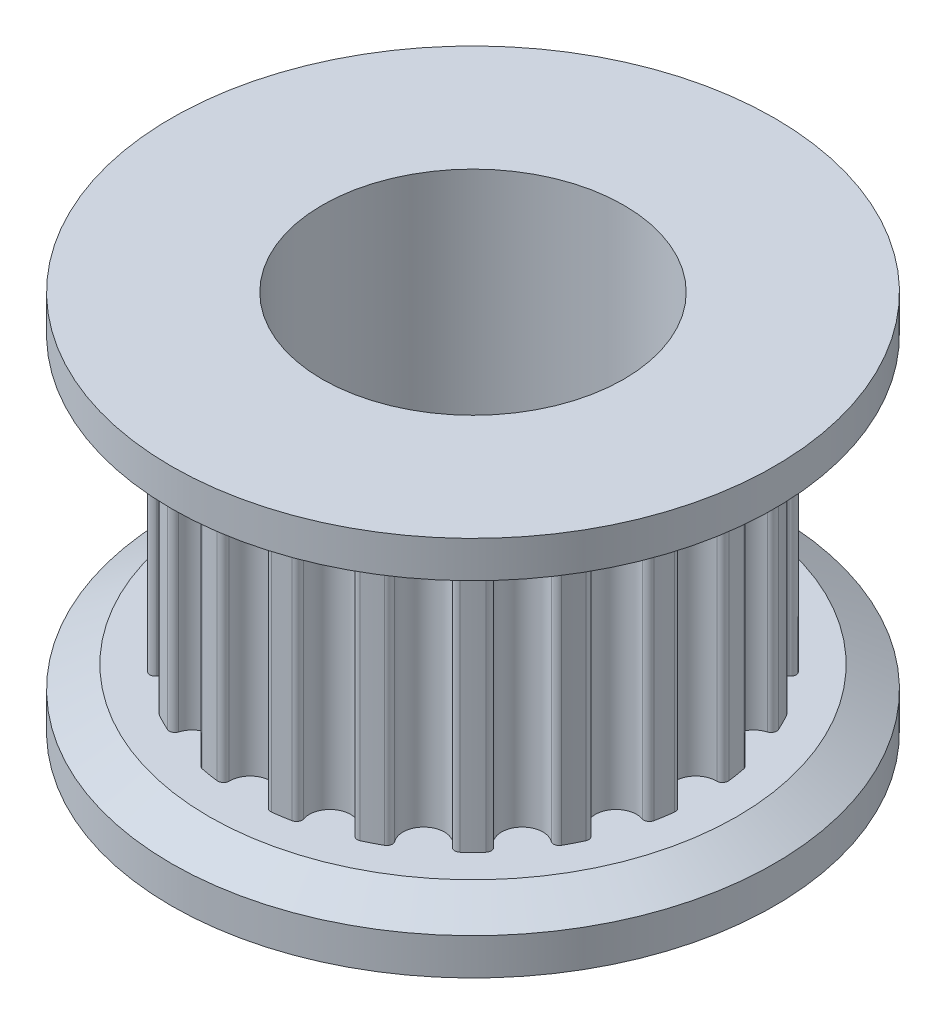
SolidWorks part; units mm, degrees
note: '?' marks a value the reader was unsure of.
material "1060 Сплав"
ref_plane "Спереди" through (0, 0, 0) normal (0, 0, 1) x (1, 0, 0)
ref_plane "Сверху" through (0, 0, 0) normal (0, 1, 0) x (1, 0, 0)
ref_plane "Справа" through (0, 0, 0) normal (1, 0, 0) x (0, 0, -1)
other "Configuration Table"
sketch "Эскиз1" plane through (0, 0, 0) normal (0, 1, 0) x (1, 0, 0)
  circle A0 centre (0, 0) radius 8
  circle A1 centre (0, 0) radius 2.5
  dimension "D1" = 16
  dimension "D2" = 5
extrude "Бобышка-Вытянуть1" add sketch "Эскиз1" along normal blind 7.45
sketch "Эскиз2" plane through (0, 7.45, 0) normal (0, 1, 0) x (1, 0, 0)
  arc A0 (-2.5575, 5.549) -> (-2.986, 5.3307) centre (0, 0) ccw
  circle A1 centre (0, 0) radius 2.5 construction
  circle A2 centre (0, 0) radius 2.5
  arc A3 (-0.55, 5.9169) -> (0.55, 5.9169) centre (0, 5.91) ccw
  arc A4 (1.3054, 5.7972) -> (2.3515, 5.4573) centre (1.8263, 5.6207) ccw
  arc A5 (3.0329, 5.1101) -> (3.9228, 4.4636) centre (3.4738, 4.7813) ccw
  arc A6 (4.4636, 3.9228) -> (5.1101, 3.0329) centre (4.7813, 3.4738) ccw
  arc A7 (5.4573, 2.3515) -> (5.7972, 1.3054) centre (5.6207, 1.8263) ccw
  arc A8 (5.9169, 0.55) -> (5.9169, -0.55) centre (5.91, 0) ccw
  arc A9 (5.7972, -1.3054) -> (5.4573, -2.3515) centre (5.6207, -1.8263) ccw
  arc A10 (5.1101, -3.0329) -> (4.4636, -3.9228) centre (4.7813, -3.4738) ccw
  arc A11 (3.9228, -4.4636) -> (3.0329, -5.1101) centre (3.4738, -4.7813) ccw
  arc A12 (2.3515, -5.4573) -> (1.3054, -5.7972) centre (1.8263, -5.6207) ccw
  arc A13 (0.55, -5.9169) -> (-0.55, -5.9169) centre (0, -5.91) ccw
  arc A14 (-1.3054, -5.7972) -> (-2.3515, -5.4573) centre (-1.8263, -5.6207) ccw
  arc A15 (-3.0329, -5.1101) -> (-3.9228, -4.4636) centre (-3.4738, -4.7813) ccw
  arc A16 (-4.4636, -3.9228) -> (-5.1101, -3.0329) centre (-4.7813, -3.4738) ccw
  arc A17 (-5.4573, -2.3515) -> (-5.7972, -1.3054) centre (-5.6207, -1.8263) ccw
  arc A18 (-5.9169, -0.55) -> (-5.9169, 0.55) centre (-5.91, 0) ccw
  arc A19 (-5.7972, 1.3054) -> (-5.4573, 2.3515) centre (-5.6207, 1.8263) ccw
  arc A20 (-5.1101, 3.0329) -> (-4.4636, 3.9228) centre (-4.7813, 3.4738) ccw
  arc A21 (-3.9228, 4.4636) -> (-3.0329, 5.1101) centre (-3.4738, 4.7813) ccw
  arc A22 (-2.3515, 5.4573) -> (-1.3054, 5.7972) centre (-1.8263, 5.6207) ccw
  arc A23 (-4.147, 4.4871) -> (-4.4871, 4.147) centre (0, 0) ccw
  arc A24 (-0.7176, 6.0677) -> (-1.1926, 5.9925) centre (0, 0) ccw
  arc A25 (1.1926, 5.9925) -> (0.7176, 6.0677) centre (0, 0) ccw
  arc A26 (2.986, 5.3307) -> (2.5575, 5.549) centre (0, 0) ccw
  arc A27 (4.4871, 4.147) -> (4.147, 4.4871) centre (0, 0) ccw
  arc A28 (5.549, 2.5575) -> (5.3307, 2.986) centre (0, 0) ccw
  arc A29 (6.0677, 0.7176) -> (5.9925, 1.1926) centre (0, 0) ccw
  arc A30 (-5.3307, 2.986) -> (-5.549, 2.5575) centre (0, 0) ccw
  arc A31 (-5.9925, 1.1926) -> (-6.0677, 0.7176) centre (0, 0) ccw
  arc A32 (-6.0677, -0.7176) -> (-5.9925, -1.1926) centre (0, 0) ccw
  arc A33 (-5.549, -2.5575) -> (-5.3307, -2.986) centre (0, 0) ccw
  arc A34 (-4.4871, -4.147) -> (-4.147, -4.4871) centre (0, 0) ccw
  arc A35 (-2.986, -5.3307) -> (-2.5575, -5.549) centre (0, 0) ccw
  arc A36 (5.9925, -1.1926) -> (6.0677, -0.7176) centre (0, 0) ccw
  arc A37 (5.3307, -2.986) -> (5.549, -2.5575) centre (0, 0) ccw
  arc A38 (4.147, -4.4871) -> (4.4871, -4.147) centre (0, 0) ccw
  arc A39 (2.5575, -5.549) -> (2.986, -5.3307) centre (0, 0) ccw
  arc A40 (0.7176, -6.0677) -> (1.1926, -5.9925) centre (0, 0) ccw
  arc A41 (-1.1926, -5.9925) -> (-0.7176, -6.0677) centre (0, 0) ccw
  arc A42 (5.9169, 0.55) -> (6.0677, 0.7176) centre (5.9188, 0.6999) ccw
  arc A43 (5.7972, 1.3054) -> (5.9925, 1.1926) centre (5.8454, 1.1633) cw
  arc A44 (5.4573, 2.3515) -> (5.549, 2.5575) centre (5.4128, 2.4947) ccw
  arc A45 (5.1101, 3.0329) -> (5.3307, 2.986) centre (5.1998, 2.9127) cw
  arc A46 (5.1101, -3.0329) -> (5.3307, -2.986) centre (5.1998, -2.9127) ccw
  arc A47 (5.4573, -2.3515) -> (5.549, -2.5575) centre (5.4128, -2.4947) cw
  arc A48 (5.7972, -1.3054) -> (5.9925, -1.1926) centre (5.8454, -1.1633) ccw
  arc A49 (5.9169, -0.55) -> (6.0677, -0.7176) centre (5.9188, -0.6999) cw
  arc A50 (3.9228, -4.4636) -> (4.147, -4.4871) centre (4.0452, -4.377) ccw
  arc A51 (4.4636, -3.9228) -> (4.4871, -4.147) centre (4.377, -4.0452) cw
  arc A52 (3.0329, -5.1101) -> (2.986, -5.3307) centre (2.9127, -5.1998) cw
  arc A53 (1.3054, -5.7972) -> (1.1926, -5.9925) centre (1.1633, -5.8454) cw
  arc A54 (0.55, -5.9169) -> (0.7176, -6.0677) centre (0.6999, -5.9188) ccw
  arc A55 (-0.55, -5.9169) -> (-0.7176, -6.0677) centre (-0.6999, -5.9188) cw
  arc A56 (-1.3054, -5.7972) -> (-1.1926, -5.9925) centre (-1.1633, -5.8454) ccw
  arc A57 (-2.3515, -5.4573) -> (-2.5575, -5.549) centre (-2.4947, -5.4128) cw
  arc A58 (-3.0329, -5.1101) -> (-2.986, -5.3307) centre (-2.9127, -5.1998) ccw
  arc A59 (-3.9228, -4.4636) -> (-4.147, -4.4871) centre (-4.0452, -4.377) cw
  arc A60 (-4.4636, -3.9228) -> (-4.4871, -4.147) centre (-4.377, -4.0452) ccw
  arc A61 (-5.9169, -0.55) -> (-6.0677, -0.7176) centre (-5.9188, -0.6999) ccw
  arc A62 (-5.7972, -1.3054) -> (-5.9925, -1.1926) centre (-5.8454, -1.1633) cw
  arc A63 (-5.4573, -2.3515) -> (-5.549, -2.5575) centre (-5.4128, -2.4947) ccw
  arc A64 (-5.1101, -3.0329) -> (-5.3307, -2.986) centre (-5.1998, -2.9127) cw
  arc A65 (-5.1101, 3.0329) -> (-5.3307, 2.986) centre (-5.1998, 2.9127) ccw
  arc A66 (-5.4573, 2.3515) -> (-5.549, 2.5575) centre (-5.4128, 2.4947) cw
  arc A67 (-5.7972, 1.3054) -> (-5.9925, 1.1926) centre (-5.8454, 1.1633) ccw
  arc A68 (-5.9169, 0.55) -> (-6.0677, 0.7176) centre (-5.9188, 0.6999) cw
  arc A69 (-4.4636, 3.9228) -> (-4.4871, 4.147) centre (-4.377, 4.0452) cw
  arc A70 (-3.9228, 4.4636) -> (-4.147, 4.4871) centre (-4.0452, 4.377) ccw
  arc A71 (-3.0329, 5.1101) -> (-2.986, 5.3307) centre (-2.9127, 5.1998) cw
  arc A72 (-2.3515, 5.4573) -> (-2.5575, 5.549) centre (-2.4947, 5.4128) ccw
  arc A73 (-1.3054, 5.7972) -> (-1.1926, 5.9925) centre (-1.1633, 5.8454) cw
  arc A74 (-0.55, 5.9169) -> (-0.7176, 6.0677) centre (-0.6999, 5.9188) ccw
  arc A75 (4.4636, 3.9228) -> (4.4871, 4.147) centre (4.377, 4.0452) ccw
  arc A76 (3.9228, 4.4636) -> (4.147, 4.4871) centre (4.0452, 4.377) cw
  arc A77 (0.55, 5.9169) -> (0.7176, 6.0677) centre (0.6999, 5.9188) cw
  arc A78 (1.3054, 5.7972) -> (1.1926, 5.9925) centre (1.1633, 5.8454) ccw
  arc A79 (3.0329, 5.1101) -> (2.986, 5.3307) centre (2.9127, 5.1998) ccw
  arc A80 (2.3515, 5.4573) -> (2.5575, 5.549) centre (2.4947, 5.4128) cw
  arc A81 (2.3515, -5.4573) -> (2.5575, -5.549) centre (2.4947, -5.4128) ccw
  point P69 (0, 0)
  point P135 (-0.5205, 6.0878)
  point P142 (0.5205, 6.0878)
  dimension "D1" = 12.22
  dimension "D2" = 1.1
  dimension "D3" = 0.75
  dimension "D5" = 0.15
  dimension "D6" = 0.15
  dimension "D4" = 20
extrude "Бобышка-Вытянуть2" add sketch "Эскиз2" along normal blind 7
sketch "Эскиз3" plane through (0, 14.45, 0) normal (0, 1, 0) x (1, 0, 0)
  circle A0 centre (0, 0) radius 2.5 construction
  circle A1 centre (0, 0) radius 2.5
  circle A2 centre (0, 0) radius 8 construction
  circle A3 centre (0, 0) radius 8
extrude "Бобышка-Вытянуть3" add sketch "Эскиз3" along normal blind 1.55
sketch "Эскиз4" plane through (0, 0, 0) normal (0, 0, 1) x (1, 0, 0)
  line L0 (-8, 3.725) -> (8, 3.725) construction
  line L1 (-8, 7.45) -> (-8, 0) construction
  line L2 (8, 0) -> (8, 7.45) construction
  circle A0 centre (0, 3.725) radius 1.25
  dimension "D1" = 2.5
extrude "Вырез-Вытянуть1" cut sketch "Эскиз4" along normal up to surface (7.9017 mm away)
sketch "Эскиз5" plane through (0, 0, 0) normal (1, 0, 0) x (0, 0, -1)
  line L0 (8, 3.725) -> (-7.9017, 3.725) construction
  line L1 (8, 0) -> (8, 7.45) construction
  circle A0 centre (0, 3.725) radius 1.25
  spline S1 degree 2 poles (-8, 4.975) (-7.8047, 3.725) (-8, 2.475) knots 0 0 0 1 1 1 weights 0.00675 0.008 0.00925 construction
  dimension "D1" = 2.5
extrude "Вырез-Вытянуть2" cut sketch "Эскиз5" along normal up to surface (7.9017 mm away)
sketch "Минимальный радиус ремня" plane through (0, 7.45, 0) normal (0, 1, 0) x (1, 0, 0)
  circle A0 centre (0, 0) radius 5.36
  arc A2 (-2.986, -5.3307) -> (-2.5575, -5.549) centre (0, 0) ccw construction
  dimension "D1" = 0.75
  dimension "D2" = 10.72
chamfer "Фаска1" distance 1 angle 30 2 edges at (0, 14.45, 8) (0, 7.45, 8)
ref_axis "Ось1" through (0, 16, 0) along (0, -1, 0)?
sketch "Esboço1" plane through (0, 0, 0) normal (0, -1, 0) x (1, 0, 0)
  circle A0 centre (0, 0) radius 8
extrude "Corte-extrusão1" cut sketch "Esboço1" against normal blind 5.9
sketch "Esboço2" plane through (0, 16, 0) normal (0, 1, 0) x (1, 0, 0)
  circle A0 centre (0, 0) radius 4
  dimension "D1" = 8
extrude "Corte-extrusão2" cut sketch "Esboço2" against normal up to surface (10.1 mm away) up to face at (0, 5.9, -2.5)
